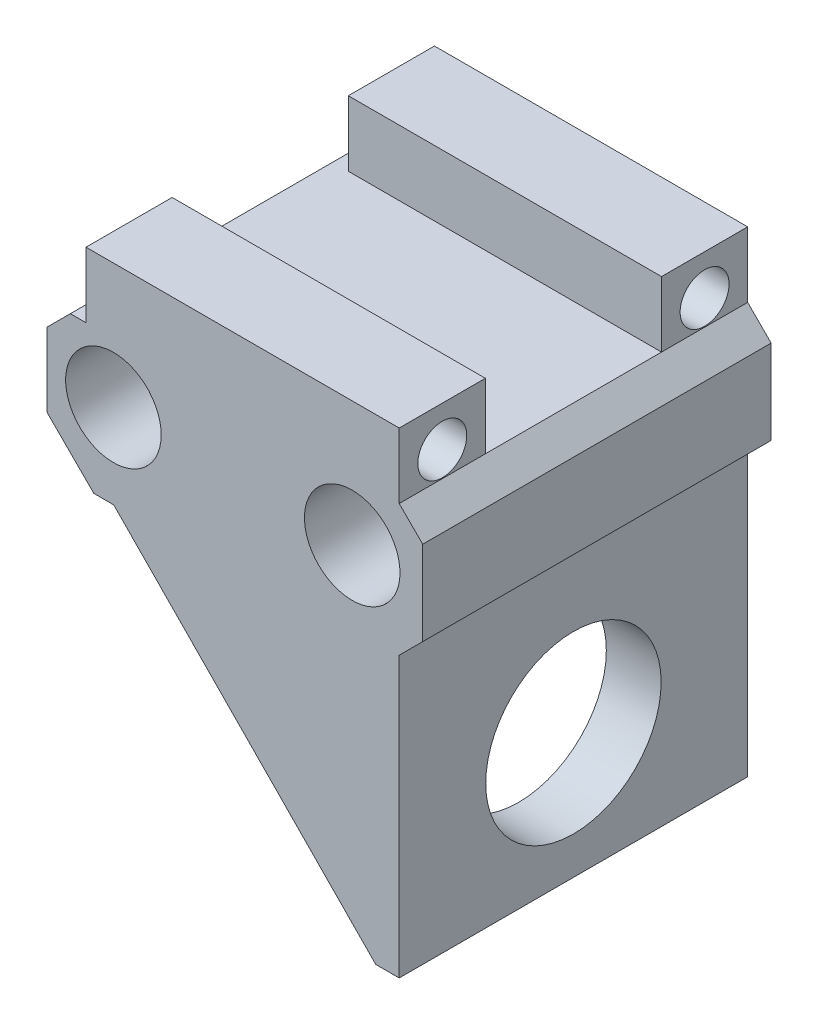
SolidWorks part; units mm, degrees
ref_plane "Front Plane" through (0, 0, 0) normal (0, 0, 1) x (1, 0, 0)
ref_plane "Top Plane" through (0, 0, 0) normal (0, 1, 0) x (1, 0, 0)
ref_plane "Right Plane" through (0, 0, 0) normal (1, 0, 0) x (0, 0, -1)
sketch "Sketch1" plane through (0, 0, 0) normal (0, 0, 1) x (1, 0, 0)
  line L0 (-37.9035, 31.8856) -> (4.5965, 31.8856)
  line L1 (-37.9035, 31.8856) -> (-37.9035, -23.9644)
  line L2 (-37.9035, -23.9644) -> (4.5965, -23.9644)
  line L3 (4.5965, -23.9644) -> (4.5965, 31.8856)
  dimension "D1" = 42.5
  dimension "D2" = 55.85
extrude "Boss-Extrude2" add sketch "Sketch1" along normal blind 42.5
sketch "Sketch5" plane through (0, 0, 42.5) normal (0, 0, 1) x (1, 0, 0)
  line L0 (-31.9035, 31.8856) -> (-31.9035, 20.046) construction
  line L1 (4.5965, 31.8856) -> (-37.9035, 31.8856) construction
  line L2 (-37.9035, 25.8856) -> (-26.7205, 25.8856) construction
  line L3 (-37.9035, 31.8856) -> (-37.9035, -23.9644) construction
  line L4 (-16.6535, 31.8856) -> (-16.6535, 20.4837) construction
  circle A0 centre (-31.9035, 25.9658) radius 3.175
  circle A1 centre (-1.4035, 25.9658) radius 3.175
  dimension "D3" = 6.35
  dimension "D1" = 6
  dimension "D2" = 6
extrude "Cut-Extrude2" cut sketch "Sketch5" against normal blind 42.5
sketch "Sketch6" plane through (-37.9035, 0, 0) normal (-1, 0, 0) x (0, 0, 1)
  line L0 (21.25, 22.7908) -> (21.25, -23.9644) construction
  line L1 (0, 22.7908) -> (42.5, 22.7908) construction
  line L2 (42.5, -23.9644) -> (0, -23.9644) construction
  line L3 (21.25, -0.5868) -> (0, -0.5868) construction
  line L4 (0, 31.8856) -> (0, -23.9644) construction
  line L5 (0, 20.6632) -> (42.5, 20.6632)
  line L6 (42.5, 31.8856) -> (42.5, -23.9644) construction
  line L7 (42.5, 20.6632) -> (42.5, -21.8368)
  line L8 (42.5, -21.8368) -> (0, -21.8368)
  line L9 (0, -21.8368) -> (0, 20.6632)
  dimension "D1" = 42.5
extrude "Cut-Extrude3" cut sketch "Sketch6" against normal blind 39.5
sketch "Sketch7" plane through (4.5965, 0, 0) normal (1, 0, 0) x (0, 0, -1)
  line L0 (-21.25, -21.8368) -> (-21.25, 20.6632) construction
  line L1 (0, -21.8368) -> (-42.5, -21.8368) construction
  line L2 (-42.5, 20.6632) -> (0, 20.6632) construction
  line L3 (-42.5, 20.6632) -> (0, 20.6632) construction
  line L4 (-42.5, -23.9644) -> (-42.5, 31.8856) construction
  line L5 (-42.5, -0.5868) -> (0, -0.5868) construction
  line L6 (0, 20.6632) -> (0, -21.8368) construction
  line L7 (0, -21.8368) -> (-42.5, -21.8368) construction
  line L8 (-42.5, -21.8368) -> (-42.5, 20.6632) construction
  line L9 (-42.5, -16.3368) -> (0, -16.3368) construction
  line L10 (-37, 20.6632) -> (-37, -21.8368) construction
  line L11 (-42.5, 14.6632) -> (0, 14.6632) construction
  circle A0 centre (-21.25, -0.5868) radius 12
  circle A1 centre (-37, -16.3368) radius 1.5
  circle A2 centre (-5.5, -16.3368) radius 1.5
  circle A3 centre (-37, 14.6632) radius 1.5
  circle A4 centre (-5.5, 14.6632) radius 1.5
  dimension "D1" = 5.5
  dimension "D3" = 31
  dimension "D2" = 5.5
  dimension "D4" = 6
extrude "Cut-Extrude4" cut sketch "Sketch7" against normal blind 39.5
sketch "Sketch9" plane through (0, -23.9644, 0) normal (0, -1, 0) x (1, 0, 0)
  line L0 (-37.9035, 42.5) -> (-27.9035, 42.5)
  line L1 (-37.9035, 42.5) -> (4.5965, 42.5) construction
  line L2 (-27.9035, 42.5) -> (-27.9035, 0)
  line L3 (-37.9035, 0) -> (4.5965, 0) construction
  line L4 (-27.9035, 0) -> (-37.9035, 0)
  line L5 (-37.9035, 0) -> (-37.9035, 42.5)
extrude "Cut-Extrude5" cut sketch "Sketch9" against normal blind 39.5
chamfer "Chamfer1" distance 3 angle 45 2 edges at (-37.9035, 31.8856, 21.25) (-37.9035, 20.6632, 21.25)
chamfer "Chamfer2" distance 2 angle 45 1 edges at (4.5965, -23.9644, 21.25)
sketch "Sketch10" plane through (-27.9035, 0, 0) normal (-1, 0, 0) x (0, 0, 1)
  line L1 (42.5, -23.9644) -> (44.5, -23.9644)
  line L4 (42.5, -21.8368) -> (44.5, -21.8368)
  line L5 (44.5, -21.8368) -> (44.5, -23.9644)
  line L7 (42.5, -21.8368) -> (42.5, -23.9644)
  line L8 (21.25, -21.8368) -> (21.25, -23.9644) construction
  line L9 (0, -21.8368) -> (42.5, -21.8368) construction
  line L10 (0, -23.9644) -> (42.5, -23.9644) construction
  line L11 (0, -21.8368) -> (-2, -21.8368)
  line L12 (-2, -21.8368) -> (-2, -23.9644)
  line L13 (0, -23.9644) -> (-2, -23.9644)
  line L14 (0, -21.8368) -> (0, -23.9644)
  dimension "D1" = 2
extrude "Boss-Extrude3" add sketch "Sketch10" against normal blind 3
sketch "Sketch12" plane through (1.5965, 0, 0) normal (-1, 0, 0) x (0, 0, 1)
  line L0 (42.5, 20.6632) -> (42.5, 17.6632)
  line L1 (42.5, -21.8368) -> (42.5, 20.6632) construction
  line L2 (42.5, 17.6632) -> (44.5, 17.6632)
  line L3 (44.5, 17.6632) -> (44.5, 20.6632)
  line L4 (44.5, 20.6632) -> (42.5, 20.6632)
  line L5 (21.25, 20.6632) -> (21.25, -21.8368) construction
  line L6 (42.5, 20.6632) -> (0, 20.6632) construction
  line L7 (-2, -21.8368) -> (44.5, -21.8368) construction
  line L8 (-2, 17.6632) -> (-2, 20.6632)
  line L9 (0, 17.6632) -> (-2, 17.6632)
  line L10 (0, 20.6632) -> (0, 17.6632)
  line L11 (-2, 20.6632) -> (0, 20.6632)
  dimension "D1" = 3
extrude "Boss-Extrude4" add sketch "Sketch12" against normal blind 3
sketch "Sketch13" plane through (0, 0, -2) normal (0, 0, -1) x (-1, 0, 0)
  line L0 (-1.5965, 17.6632) -> (24.9035, -21.8368)
  line L1 (-1.5965, 20.6632) -> (27.9035, -21.8368)
  line L2 (27.9035, -21.8368) -> (24.9035, -21.8368)
  line L3 (-1.5965, 20.6632) -> (-1.5965, 17.6632)
extrude "Boss-Extrude5" add sketch "Sketch13" against normal blind 2
sketch "Sketch14" plane through (0, 0, 44.5) normal (0, 0, 1) x (1, 0, 0)
  line L0 (1.5965, 17.6632) -> (-24.9035, -21.8368)
  line L1 (-24.9035, -21.8368) -> (-27.9035, -21.8368)
  line L2 (-27.9035, -21.8368) -> (1.5965, 20.6632)
  line L3 (1.5965, 20.6632) -> (1.5965, 17.6632)
extrude "Boss-Extrude6" add sketch "Sketch14" against normal blind 2
sketch "Sketch16" plane through (4.5965, 0, 0) normal (1, 0, 0) x (0, 0, -1)
  line L0 (-42.5, 30.0689) -> (-33.5, 30.0689)
  line L1 (-38, 42.2389) -> (-30.3717, 42.2389) construction
  line L2 (-42.5, 20.6632) -> (-42.5, 31.8856) construction
  line L3 (-33.5, 30.0689) -> (-33.5, 44.2389)
  line L4 (-33.5, 44.2389) -> (-42.5, 44.2389)
  line L5 (-42.5, 44.2389) -> (-42.5, 30.0689)
  line L6 (-21.25, 31.8856) -> (-21.25, 36.9569) construction
  line L7 (-42.5, 31.8856) -> (0, 31.8856) construction
  line L8 (-9, 44.2389) -> (0, 44.2389)
  line L9 (-9, 30.0689) -> (-9, 44.2389)
  line L10 (0, 30.0689) -> (-9, 30.0689)
  line L11 (0, 44.2389) -> (0, 30.0689)
  line L12 (-33.5, 44.2389) -> (-30.3717, 44.2389) construction
  circle A0 centre (-38, 39.1139) radius 3.125
  circle A1 centre (-4.5, 39.1139) radius 3.125
  dimension "D3" = 6.25
  dimension "D4" = 2
  dimension "D1" = 9
  dimension "D2" = 14.17
extrude "Boss-Extrude8" add sketch "Sketch16" against normal blind 5
sketch "Sketch18" plane through (-0.4035, 0, 0) normal (-1, 0, 0) x (0, 0, 1)
  line L0 (0, 44.2389) -> (9, 44.2389)
  line L1 (9, 44.2389) -> (9, 31.8856)
  line L2 (9, 31.8856) -> (0, 31.8856)
  line L3 (0, 31.8856) -> (0, 44.2389)
  line L4 (21.25, 39.3131) -> (21.25, 31.8856) construction
  line L5 (0, 31.8856) -> (42.5, 31.8856) construction
  line L6 (33.5, 31.8856) -> (42.5, 31.8856)
  line L7 (33.5, 44.2389) -> (33.5, 31.8856)
  line L8 (42.5, 44.2389) -> (33.5, 44.2389)
  line L9 (42.5, 31.8856) -> (42.5, 44.2389)
extrude "Boss-Extrude9" add sketch "Sketch18" along normal blind 2
sketch "Sketch20" plane through (0, 0, 42.5) normal (0, 0, 1) x (1, 0, 0)
  line L0 (-34.9035, 20.6632) -> (1.5965, 20.6632)
  line L1 (1.5965, 20.6632) -> (1.5965, -24.5984)
  line L2 (1.5965, -24.5984) -> (-34.9035, -24.5984)
  line L3 (-34.9035, -24.5984) -> (-34.9035, 20.6632)
extrude "Cut-Extrude9" cut sketch "Sketch20" against normal mid plane 132
sketch "Sketch21" plane through (4.5965, 0, 0) normal (1, 0, 0) x (0, 0, -1)
  line L0 (0, 44.2389) -> (0, -21.9644)
  line L1 (0, -21.9644) -> (2.4617, -21.9644)
  line L2 (2.4617, -21.9644) -> (3.038, 44.2389)
  line L3 (3.038, 44.2389) -> (0.568, 44.2389)
  line L4 (0, 44.2389) -> (0.568, 44.2389)
  line L5 (-21.25, -21.9644) -> (-21.25, 31.8856) construction
  line L6 (-42.5, -21.9644) -> (0, -21.9644) construction
  line L7 (-33.5, 31.8856) -> (-9, 31.8856) construction
  line L8 (-42.5, 44.2389) -> (-42.5, -21.9644)
  line L9 (-42.5, -21.9644) -> (-44.9617, -21.9644)
  line L10 (-44.9617, -21.9644) -> (-45.538, 44.2389)
  line L11 (-45.538, 44.2389) -> (-43.068, 44.2389)
  line L12 (-42.5, 44.2389) -> (-43.068, 44.2389)
extrude "Cut-Extrude10" cut sketch "Sketch21" against normal mid plane 132
sketch "Sketch22" plane through (4.5965, 0, 0) normal (1, 0, 0) x (0, 0, -1)
  circle A0 centre (-21.25, -0.5893) radius 11.2
  circle A1 centre (-21.25, -0.4993) radius 12.5
  circle A2 centre (-37, 14.6632) radius 2
  circle A3 centre (-5.5246, 14.7507) radius 2
  circle A4 centre (-5.5, -16.3368) radius 2
  circle A5 centre (-37, -16.3368) radius 2
  dimension "D1" = 22.4
  dimension "D2" = 0.09
extrude "Boss-Extrude13" add sketch "Sketch22" against normal blind 3
sketch "Sketch23" plane through (4.5965, 0, 0) normal (1, 0, 0) x (0, 0, -1)
  line L0 (-42.5, -16.5893) -> (0, -16.5893)
  line L1 (-42.5, -21.9644) -> (-42.5, 44.2389) construction
  line L2 (0, -21.9644) -> (0, 44.2389) construction
  line L3 (0, -16.5893) -> (0, -23.9644)
  line L4 (0, -23.9644) -> (-42.5, -23.9644)
  line L5 (-42.5, -23.9644) -> (-42.5, -21.9644) construction
  line L6 (0, -23.9644) -> (-42.5, -23.9644) construction
  line L7 (-42.5, -23.9644) -> (-42.5, -16.5893)
  circle A0 centre (-21.25, -0.5893) radius 11.2 construction
  dimension "D1" = 16
extrude "Cut-Extrude11" cut sketch "Sketch23" against normal blind 3
chamfer "Chamfer3" distance 2 angle 45 1 edges at (4.5965, -16.5893, 21.25)
sketch "Sketch24" plane through (1.5965, 0, 0) normal (-1, 0, 0) x (0, 0, 1)
  circle A0 centre (21.25, -0.5893) radius 11.2
  circle A1 centre (21.25, -0.5893) radius 13.75
  dimension "D1" = 27.5
  dimension "D2" = 22.4
extrude "Boss-Extrude14" add sketch "Sketch24" along normal blind 4
sketch "Sketch25" plane through (0, 0, 42.5) normal (0, 0, 1) x (1, 0, 0)
  line L0 (-34.9035, 20.6632) -> (1.5965, -16.5893)
  line L1 (1.5965, -16.5893) -> (1.5965, 20.6632)
  line L2 (1.5965, 20.6632) -> (-34.9035, 20.6632)
extrude "Boss-Extrude15" add sketch "Sketch25" against normal blind 2.5
sketch "Sketch26" plane through (0, 0, 0) normal (0, 0, -1) x (-1, 0, 0)
  line L0 (-1.5965, 20.6632) -> (-1.5965, -16.5893)
  line L1 (-1.5965, -16.5893) -> (34.9035, 20.6632)
  line L2 (34.9035, 20.6632) -> (-1.5965, 20.6632)
extrude "Boss-Extrude16" add sketch "Sketch26" against normal blind 2.5
sketch "Sketch28" plane through (0, 0, 42.5) normal (0, 0, 1) x (1, 0, 0)
  line L0 (4.5965, -14.5893) -> (1.5965, -14.5893)
  line L1 (1.5965, -14.5893) -> (1.5965, -16.5893)
  line L2 (-34.9035, 20.6632) -> (1.5965, -16.5893) construction
  line L3 (1.5965, -16.5893) -> (4.5965, -16.5893)
  line L4 (4.5965, -16.5893) -> (4.5965, -14.5893)
extrude "Boss-Extrude17" add sketch "Sketch28" against normal blind 42.5
sketch "Sketch29" plane through (4.5965, 0, 0) normal (1, 0, 0) x (0, 0, -1)
  line L0 (-21.25, 31.8856) -> (-21.25, 39.7009) construction
  line L1 (-33.5, 31.8856) -> (-9, 31.8856) construction
  line L2 (-33.5, 44.2389) -> (-33.5, 31.8856)
  line L3 (-33.5, 31.8856) -> (-32.5, 31.8856)
  line L4 (-33.5, 44.2389) -> (-32.5, 44.2389)
  line L5 (-32.5, 44.2389) -> (-32.5, 31.8856)
  line L6 (-9, 44.2389) -> (-10, 44.2389)
  line L7 (-9, 44.2389) -> (-9, 31.8856)
  line L8 (-9, 31.8856) -> (-10, 31.8856)
  line L9 (-10, 44.2389) -> (-10, 31.8856)
extrude "Boss-Extrude18" add sketch "Sketch29" against normal blind 7
sketch "Sketch31" plane through (0, 0, 42.5) normal (0, 0, 1) x (1, 0, 0)
  line L0 (-37.9035, 28.8856) -> (-37.9035, 23.6632)
  line L1 (-37.9035, 23.6632) -> (1.5965, -16.5893)
  line L2 (1.5965, -16.5893) -> (4.5965, -16.5893)
  line L3 (4.5965, -16.5893) -> (4.5965, 44.2389)
  line L4 (4.5965, 44.2389) -> (-2.4035, 44.2389)
  line L5 (-2.4035, 44.2389) -> (-2.4035, 31.8856)
  line L6 (-2.4035, 31.8856) -> (-34.9035, 31.8856)
  line L7 (-34.9035, 31.8856) -> (-37.9035, 28.8856)
  circle A0 centre (-31.9035, 25.9658) radius 3.175
  circle A1 centre (-1.4035, 25.9658) radius 3.175
extrude "Boss-Extrude19" add sketch "Sketch31" along normal blind 1
sketch "Sketch32" plane through (0, 0, 0) normal (0, 0, -1) x (-1, 0, 0)
  line L0 (-4.5965, 44.2389) -> (-4.5965, -16.5893)
  line L1 (-4.5965, -16.5893) -> (-1.5965, -16.5893)
  line L2 (-1.5965, -16.5893) -> (37.9035, 23.6632)
  line L3 (37.9035, 23.6632) -> (37.9035, 28.8856)
  line L4 (37.9035, 28.8856) -> (34.9035, 31.8856)
  line L5 (34.9035, 31.8856) -> (2.4035, 31.8856)
  line L6 (2.4035, 31.8856) -> (2.4035, 44.2389)
  line L7 (2.4035, 44.2389) -> (-4.5965, 44.2389)
  circle A0 centre (1.4035, 25.9658) radius 3.175
  circle A1 centre (31.9035, 25.9658) radius 3.175
extrude "Boss-Extrude20" add sketch "Sketch32" along normal blind 1
sketch "Sketch33" plane through (-7.4798, -7.34, 0) normal (-0.7137, -0.7004, 0) x (0, 0, 1)
  line L0 (-1, 43.4373) -> (-1, -12.9587)
  line L1 (-1, -12.9587) -> (2.5, -12.9587)
  line L3 (2.5, -12.9587) -> (2.5, 39.1949)
  line L4 (2.5, 39.1949) -> (40, 39.1949)
  line L5 (40, 39.1949) -> (40, -12.9587)
  line L6 (40, -12.9587) -> (43.5, -12.9587)
  line L7 (43.5, -12.9587) -> (43.5, 43.4373)
  line L8 (43.5, 43.4373) -> (-1, 43.4373)
extrude "Boss-Extrude21" add sketch "Sketch33" against normal blind 1
sketch "Sketch34" plane through (4.5965, 0, 0) normal (1, 0, 0) x (0, 0, -1)
  line L0 (-43.5, 44.2389) -> (-32.5, 44.2389)
  line L1 (-32.5, 44.2389) -> (-32.5, 35.7389)
  line L2 (-43.5, 44.2389) -> (-43.5, 35.7389)
  line L3 (-43.5, -16.5893) -> (-43.5, 44.2389) construction
  line L4 (-43.5, 35.7389) -> (-32.5, 35.7389)
  line L5 (-10, 44.2389) -> (1, 44.2389)
  line L6 (1, 44.2389) -> (1, 30.5689)
  line L7 (1, 44.2389) -> (1, -16.5893) construction
  line L8 (1, 30.5689) -> (-10, 30.5689)
  line L9 (-10, 30.5689) -> (-10, 44.2389)
  circle A0 centre (-38, 39.1139) radius 3.125
  circle A1 centre (-4.5, 39.1139) radius 3.125
  dimension "D2" = 6.25
  dimension "D3" = 6.25
  dimension "D1" = 8.5
extrude "Boss-Extrude22" add sketch "Sketch34" against normal blind 40
sketch "Sketch35" plane through (4.5965, 0, 0) normal (1, 0, 0) x (0, 0, -1)
  circle A0 centre (-38, 39.1139) radius 3.125
  circle A1 centre (-4.5, 39.1139) radius 3.125
  dimension "D1" = 6.25
  dimension "D2" = 6.25
extrude "Cut-Extrude13" cut sketch "Sketch35" against normal blind 52
sketch "Sketch36" plane through (0, 0, 43.5) normal (0, 0, 1) x (1, 0, 0)
  line L0 (-35.4035, 35.7389) -> (-35.4035, 31.3856)
  line L1 (-35.4035, 31.3856) -> (-34.9035, 31.8856)
  line L2 (-34.9035, 31.8856) -> (-2.4035, 31.8856)
  line L3 (-2.4035, 31.8856) -> (-2.4035, 35.7389)
  line L4 (-2.4035, 35.7389) -> (-35.4035, 35.7389)
extrude "Boss-Extrude23" add sketch "Sketch36" against normal blind 11
sketch "Sketch37" plane through (4.5965, 0, 0) normal (1, 0, 0) x (0, 0, -1)
  line L0 (-32.5, 31.8856) -> (-10, 31.8856)
  line L1 (-10, 31.8856) -> (-10, 35.8856)
  line L2 (-10, 44.2389) -> (-10, 31.8856) construction
  line L3 (-10, 35.8856) -> (-32.5, 35.8856)
  line L4 (-32.5, 31.8856) -> (-32.5, 44.2389) construction
  line L5 (-32.5, 35.8856) -> (-32.5, 31.8856)
  dimension "D1" = 4
extrude "Boss-Extrude24" add sketch "Sketch37" against normal blind 43
sketch "Sketch38" plane through (0, 0, 43.5) normal (0, 0, 1) x (1, 0, 0)
  line L0 (-35.2922, 35.8856) -> (-35.2922, 21.4593)
  line L1 (-35.4035, 35.8856) -> (4.5965, 35.8856) construction
  line L2 (-35.2922, 21.4593) -> (-38.4035, 21.4593)
  line L3 (-38.4035, 21.4593) -> (-38.4035, 35.8856)
  line L4 (-38.4035, 35.8856) -> (-35.2922, 35.8856)
extrude "Boss-Extrude25" add sketch "Sketch38" against normal blind 44.5
sketch "Sketch39" plane through (0, 0, -1) normal (0, 0, -1) x (-1, 0, 0)
  line L0 (34.6527, 32.4615) -> (35.7806, 32.4615)
  line L1 (35.7806, 32.4615) -> (35.7806, 30.7382)
  line L2 (35.7806, 30.7382) -> (34.6527, 30.7382)
  line L3 (34.6527, 30.7382) -> (34.6527, 32.4615)
extrude "Boss-Extrude26" add sketch "Sketch39" against normal blind 44.5
sketch "Sketch40" plane through (0, 0, 43.5) normal (0, 0, 1) x (1, 0, 0)
  line L0 (-38.4035, 25.9658) -> (4.6965, 25.9658) construction
  line L1 (-38.4035, 35.8856) -> (-38.4035, 21.4593) construction
  line L2 (-38.4035, 28.2658) -> (4.6965, 28.2658) construction
  line L3 (-31.9035, 25.9658) -> (-31.9035, 33.201) construction
  line L4 (-1.4035, 25.9658) -> (-1.4035, 33.201) construction
  circle A0 centre (-31.9035, 28.2658) radius 6.1
  circle A1 centre (-1.4035, 28.2658) radius 6.1
  dimension "D1" = 2.3
sketch "Sketch41" plane through (0, 0, 43.5) normal (0, 0, 1) x (1, 0, 0)
  line L0 (-38.4035, 35.8856) -> (-40.4035, 35.8856)
  line L1 (-40.4035, 35.8856) -> (-40.4035, 21.4593)
  line L2 (-40.4035, 21.4593) -> (-40.4035, 17.5066)
  line L3 (-40.4035, 17.5066) -> (-31.8619, 17.5066)
  line L4 (-35.7408, 21.4593) -> (1.5965, -16.5893) construction
  line L5 (-31.8619, 17.5066) -> (-35.7408, 21.4593)
  line L6 (-35.7408, 21.4593) -> (-38.4035, 21.4593)
  line L7 (-38.4035, 21.4593) -> (-38.4035, 35.8856)
extrude "Boss-Extrude27" add sketch "Sketch41" against normal blind 44.5
sketch "Sketch42" plane through (0, 0, 43.5) normal (0, 0, 1) x (1, 0, 0)
  line L0 (4.5965, 35.8856) -> (6.5965, 35.8856)
  line L1 (4.5965, -16.5893) -> (4.5965, 44.2389) construction
  line L2 (6.5965, 35.8856) -> (6.5965, 19.1143)
  line L3 (6.5965, 19.1143) -> (4.5965, 19.1143)
  line L4 (4.5965, 19.1143) -> (4.5965, 35.8856)
  dimension "D1" = 2
extrude "Boss-Extrude28" add sketch "Sketch42" against normal blind 44.5
chamfer "Chamfer4" distance 2 angle 45 2 edges at (6.5965, 19.1143, 21.25) (6.5965, 35.8856, 21.25)
chamfer "Chamfer5" distance 3 angle 45 1 edges at (-40.4035, 35.8856, 21.25)
extrude "Cut-Extrude14" cut sketch "Sketch40" against normal blind 44.5
chamfer "Chamfer6" distance 6 angle 45 1 edges at (-40.4035, 17.5066, 21.25)
sketch "Sketch44" plane through (4.5965, 0, 0) normal (1, 0, 0) x (0, 0, -1)
  line L0 (-40, 20.6632) -> (-40, 17.5066)
  line L1 (-40, 17.5066) -> (-2.5, 17.5066)
  line L2 (-2.5, 17.5066) -> (-2.5, 20.6632)
  line L3 (-2.5, 20.6632) -> (-40, 20.6632)
extrude "Boss-Extrude32" add sketch "Sketch44" against normal blind 38.5
sketch "Sketch45" plane through (0, 0, 43.5) normal (0, 0, 1) x (1, 0, 0)
  line L0 (-35.5956, 21.2619) -> (-33.1299, 21.2619)
  line L1 (-33.1299, 21.2619) -> (-33.1299, 19.0348)
  line L2 (-33.1299, 19.0348) -> (-35.5956, 19.0348)
  line L3 (-35.5956, 19.0348) -> (-35.5956, 21.2619)
extrude "Boss-Extrude33" add sketch "Sketch45" against normal blind 44.5
sketch "Sketch47" plane through (0, 0, 43.5) normal (0, 0, 1) x (1, 0, 0)
  line L0 (6.5965, 33.8856) -> (7.5965, 32.8856)
  line L1 (7.5965, 32.8856) -> (7.5965, 22.1143)
  line L2 (7.5965, 22.1143) -> (6.5965, 21.1143)
  line L3 (6.5965, 21.1143) -> (6.5965, 33.8856)
  line L4 (6.5965, 33.8856) -> (4.5965, 35.8856) construction
  line L5 (4.5965, 19.1143) -> (6.5965, 21.1143) construction
  dimension "D1" = 1
extrude "Boss-Extrude34" add sketch "Sketch47" against normal blind 44.5
